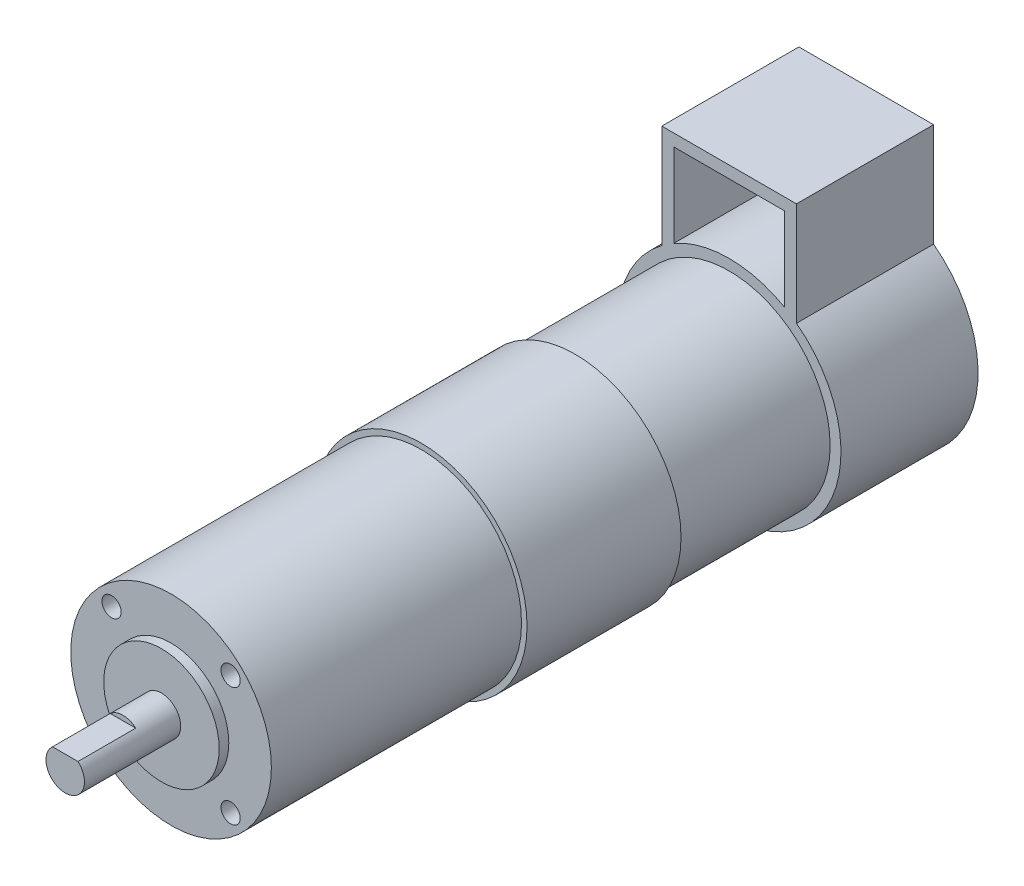
SolidWorks part; units mm, degrees
ref_plane "Front Plane" through (0, 0, 0) normal (0, 0, 1) x (1, 0, 0)
ref_plane "Top Plane" through (0, 0, 0) normal (0, 1, 0) x (1, 0, 0)
ref_plane "Right Plane" through (0, 0, 0) normal (1, 0, 0) x (0, 0, -1)
sketch "Sketch1" plane through (0, 0, 0) normal (0, 0, 1) x (1, 0, 0)
  circle A0 centre (0, 0) radius 22
  dimension "D1" = 44
extrude "Boss-Extrude1" add sketch "Sketch1" along normal blind 16 and the other way blind 16
sketch "Sketch2" plane through (0, 0, 16) normal (0, 0, 1) x (1, 0, 0)
  circle A0 centre (0, 0) radius 20.85
  dimension "D1" = 41.7
extrude "Boss-Extrude2" add sketch "Sketch2" along normal blind 8
sketch "Sketch3" plane through (0, 0, 24) normal (0, 0, 1) x (1, 0, 0)
  circle A0 centre (0, 0) radius 20.85
extrude "Boss-Extrude3" add sketch "Sketch3" along normal blind 44
sketch "Sketch4" plane through (0, 0, -16) normal (0, 0, -1) x (-1, 0, 0)
  circle A0 centre (0, 0) radius 21
  dimension "D1" = 42
extrude "Boss-Extrude4" add sketch "Sketch4" along normal blind 32
sketch "Sketch5" plane through (0, 0, -48) normal (0, 0, -1) x (-1, 0, 0)
  circle A0 centre (0, 0) radius 23.25
  dimension "D1" = 46.5
extrude "Boss-Extrude5" add sketch "Sketch5" along normal blind 28.5
sketch "Sketch6" plane through (0, 0, -76.5) normal (0, 0, -1) x (-1, 0, 0)
  line L0 (0, 0) -> (0, 50.1287) construction
  line L1 (14, 40.0624) -> (-14, 40.0624)
  line L2 (-14, 40.0624) -> (-14, 18.5624)
  line L3 (14, 40.0624) -> (14, 18.5624)
  line L4 (11.5, 37.5624) -> (11.5, 20.2067)
  line L5 (11.5, 37.5624) -> (-11.5, 37.5624)
  line L6 (-11.5, 37.5624) -> (-11.5, 20.2067)
  line L8 (-11.5, 37.5624) -> (-11.5, 18.5624) construction
  line L9 (11.5, 37.5624) -> (11.5, 18.5624) construction
  circle A0 centre (0, 0) radius 23.25 construction
  arc A2 (-11.5, 20.2067) -> (-14, 18.5624) centre (0, 0) ccw
  circle A3 centre (0, 0) radius 23.25
  arc A4 (14, 18.5624) -> (11.5, 20.2067) centre (0, 0) ccw
  point P10 (0, 40.0624)
  dimension "D1" = 14
  dimension "D2" = 21.5
  dimension "D3" = 0
  dimension "D4" = 2.5
extrude "Boss-Extrude6" add sketch "Sketch6" against normal blind 28.5 contours L2 A2 L6 L5 L4 A4 L3 L1
sketch "Sketch7" plane through (0, 0, 68) normal (0, 0, 1) x (1, 0, 0)
  circle A0 centre (0, 0) radius 12
  dimension "D1" = 24
extrude "Boss-Extrude7" add sketch "Sketch7" along normal blind 2
sketch "Sketch8" plane through (0, 0, 68) normal (0, 0, 1) x (1, 0, 0)
  line L0 (0, 0) -> (30.6806, 0) construction
  line L1 (0, 0) -> (28.4477, 28.4477) construction
  circle A0 centre (0, 0) radius 17.5 construction
  circle A1 centre (12.3744, 12.3744) radius 2
  circle A2 centre (12.3744, -12.3744) radius 2
  circle A3 centre (-12.3744, -12.3744) radius 2
  circle A4 centre (-12.3744, 12.3744) radius 2
  point P16 (0, 0)
  dimension "D1" = 35
  dimension "D2" = 45
  dimension "D3" = 4
  dimension "D4" = 4
extrude "Cut-Extrude1" cut sketch "Sketch8" against normal blind 6
sketch "Sketch9" plane through (0, 0, -76.5) normal (0, 0, -1) x (-1, 0, 0)
  line L1 (12.0601, 17.1467) -> (-12.0601, 17.1467)
  line L2 (12.0601, 17.1467) -> (12.0601, 38.1288)
  line L3 (12.0601, 38.1288) -> (-12.0601, 38.1288)
  line L4 (-12.0601, 17.1467) -> (-12.0601, 38.1288)
  line L5 (12.0601, 17.1467) -> (-12.0601, 38.1288) construction
  line L6 (12.0601, 38.1288) -> (-12.0601, 17.1467) construction
  point P0 (0, 27.6377)
extrude "Boss-Extrude8" add sketch "Sketch9" against normal blind 2
sketch "Sketch10" plane through (0, 0, 70) normal (0, 0, 1) x (1, 0, 0)
  circle A0 centre (0, 0) radius 4
  dimension "D1" = 8
extrude "Boss-Extrude9" add sketch "Sketch10" along normal blind 20
sketch "Sketch11" plane through (0, 0, 90) normal (0, 0, 1) x (1, 0, 0)
  line L0 (0, 3) -> (-3.9817, 3)
  line L1 (0, 3) -> (4.0509, 3)
  line L2 (-3.9817, 3) -> (-3.9817, 4.1928)
  line L3 (-3.9817, 4.1928) -> (4.0509, 4.1928)
  line L4 (4.0509, 4.1928) -> (4.0509, 3)
  dimension "D1" = 3
extrude "Cut-Extrude2" cut sketch "Sketch11" against normal blind 12
